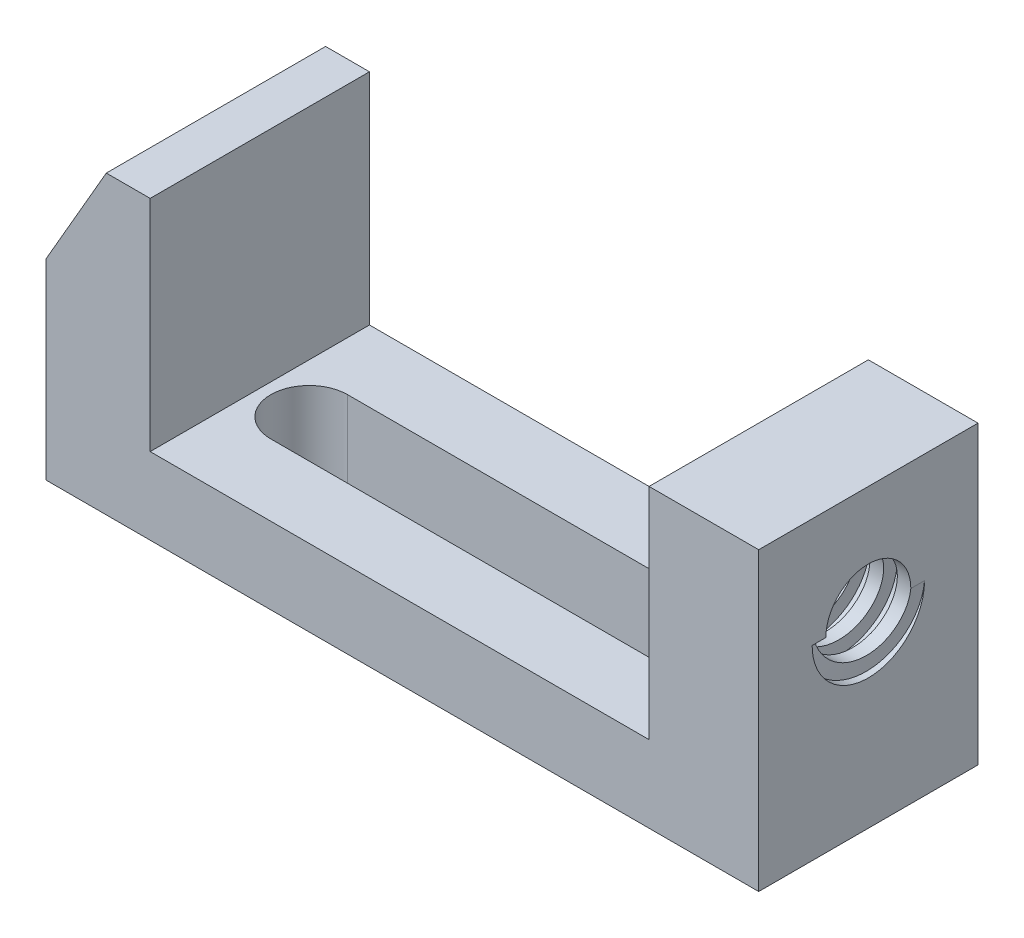
SolidWorks part; units mm, degrees
material "AISI Aço-ferramenta tipo A2"
ref_plane "Plano frontal" through (0, 0, 0) normal (0, 0, 1) x (1, 0, 0)
ref_plane "Plano superior" through (0, 0, 0) normal (0, 1, 0) x (1, 0, 0)
ref_plane "Plano direito" through (0, 0, 0) normal (1, 0, 0) x (0, 0, -1)
sketch "Esboço1" plane through (0, 0, 0) normal (0, 0, 1) x (1, 0, 0)
  line L0 (0, 0) -> (130, 0)
  line L1 (130, 0) -> (130, 54)
  line L2 (130, 54) -> (110, 54)
  line L3 (110, 54) -> (110, 14)
  line L4 (110, 14) -> (19, 14)
  line L5 (19, 14) -> (19, 54)
  line L6 (19, 54) -> (11, 54)
  line L7 (11, 54) -> (0, 34.9474)
  line L8 (0, 34.9474) -> (0, 0)
  dimension "D1" = 130
  dimension "D2" = 54
  dimension "D3" = 14
  dimension "D4" = 8
  dimension "D5" = 30
  dimension "D6" = 40
  dimension "D7" = 11
  dimension "D8" = 20
extrude "Ressalto-extrusão1" add sketch "Esboço1" against normal blind 40
sketch "Esboço2" plane through (130, 0, 0) normal (1, 0, 0) x (0, 0, -1)
  line L0 (40, 54) -> (0, 54) construction
  circle A0 centre (20, 34) radius 7.75
  point P4 (20, 54)
  dimension "D1" = 15.5
  dimension "D2" = 20
extrude "Corte-extrusão1" cut sketch "Esboço2" against normal blind 40
sketch "Esboço3" plane through (130, 0, 0) normal (1, 0, 0) x (0, 0, -1)
  circle A0 centre (20, 34) radius 7.75
curve "Hélice/Espiral1" pitch 5 height 27.5 radius 7.75 centre (130, 34, -20) axis (-1, 0, 0) start towards (0, 0, 1)
sketch "Esboço11" plane through (0, 0, 0) normal (0, -1, 0) x (1, 0, 0)
  line L1 (130, -12.25) -> (127.5, -12.25)
  line L2 (130, -12.25) -> (130, -14.75)
  line L3 (130, -14.75) -> (127.5, -14.75)
  line L4 (127.5, -12.25) -> (127.5, -14.75)
  dimension "D1" = 2.5
  dimension "D2" = 2.5
  dimension "D3" = 0
  dimension "D4" = 0
ref_plane "Plano1" through (0, 34, 0) normal (0, -1, 0) x (-1, 0, 0)
sketch "Esboço12" plane through (0, 34, 0) normal (0, -1, 0) x (-1, 0, 0)
  line L5 (-130, 12.25) -> (-127.5, 12.25)
  line L6 (-130, 12.25) -> (-130, 9.75)
  line L7 (-130, 9.75) -> (-127.5, 9.75)
  line L8 (-127.5, 12.25) -> (-127.5, 9.75)
  dimension "D1" = 2.5
  dimension "D2" = 2.5
sweep "Varredura de corte5" cut profiles "Esboço12" path "Hélice/Espiral1" align with end faces yes
sketch "Esboço14" plane through (0, 0, 0) normal (0, -1, 0) x (1, 0, 0)
  line L0 (0, -40) -> (0, 0) construction
  line L1 (0, -40) -> (130, -40) construction
  line L2 (9.5, -35) -> (46.5, -35) construction
  circle A0 centre (9.5, -35) radius 1.5875
  circle A1 centre (46.5, -35) radius 1.5875
  circle A2 centre (83.5, -35) radius 1.5875
  circle A3 centre (120.5, -35) radius 1.5875
  circle A4 centre (46.5, -5) radius 1.5875
  circle A5 centre (83.5, -5) radius 1.5875
  circle A6 centre (120.5, -5) radius 1.5875
  circle A7 centre (9.5, -5) radius 1.5875
  dimension "D1" = 3.175
  dimension "D2" = 9.5
  dimension "D3" = 5
  dimension "D6" = 37
  dimension "D4" = 4
  dimension "D5" = 2
extrude "Corte-extrusão2" cut sketch "Esboço14" against normal blind 10
sketch "Esboço15" plane through (0, 14, 0) normal (0, 1, 0) x (1, 0, 0)
  line L0 (28, 20) -> (101, 20) construction
  line L1 (28, 27) -> (101, 27)
  line L2 (28, 13) -> (101, 13)
  line L3 (0, 40) -> (0, 0) construction
  line L4 (0, 40) -> (130, 40) construction
  arc A0 (28, 27) -> (28, 13) centre (28, 20) ccw
  arc A1 (101, 13) -> (101, 27) centre (101, 20) ccw
  point P2 (64.5, 20)
  dimension "D1" = 7
  dimension "D2" = 73
  dimension "D3" = 28
  dimension "D4" = 20
extrude "Corte-extrusão3" cut sketch "Esboço15" against normal blind 20
